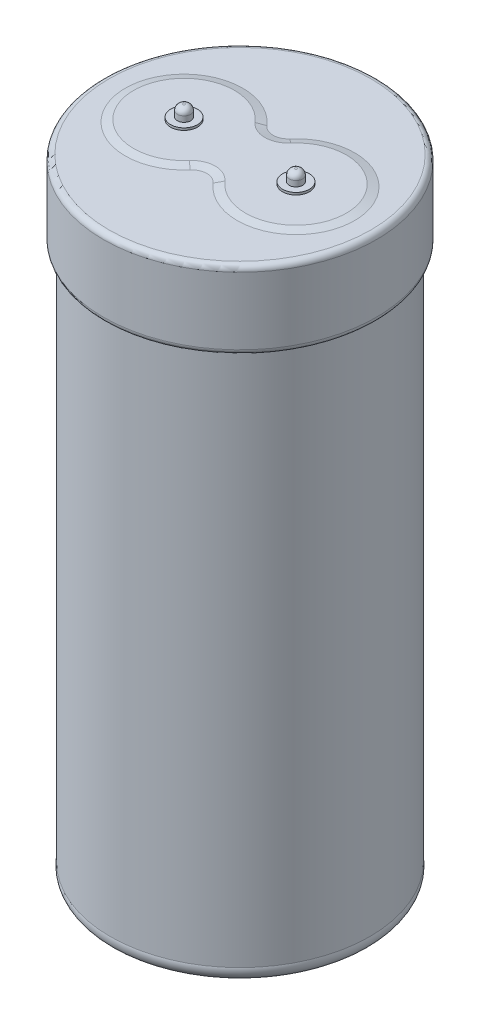
SolidWorks part; units mm, degrees
ref_plane "Front Plane" through (0, 0, 0) normal (0, 0, 1) x (1, 0, 0)
ref_plane "Top Plane" through (0, 0, 0) normal (0, 1, 0) x (1, 0, 0)
ref_plane "Right Plane" through (0, 0, 0) normal (1, 0, 0) x (0, 0, -1)
sketch "Sketch1" plane through (0, 0, 0) normal (0, 0, 1) x (1, 0, 0)
  line L0 (0, 125.4241) -> (0, -154.5759) construction
  line L1 (-1006.3009, 386.8456) -> (941.4092, 386.8456) construction
  line L2 (0, 125.4241) -> (61, 125.4241)
  line L3 (58, 90.4241) -> (58, -148.2441)
  line L4 (53.0864, -154.5759) -> (6, -154.5759)
  line L5 (0, -154.5759) -> (0, 125.4241) construction
  line L6 (6, -154.5759) -> (6, -169.7633)
  line L7 (6, -169.7633) -> (5.1874, -170.5759)
  line L8 (5.1874, -170.5759) -> (0, -170.5759)
  line L9 (0, -170.5759) -> (0, -154.5759) construction
  line L10 (6, -154.5759) -> (0, -154.5759) construction
  line L11 (61, 123.3205) -> (61, 110.2818) construction
  line L12 (0, 125.4241) -> (0, -170.5759)
  line L13 (61, 125.4241) -> (61, 90.4241)
  line L14 (61, 90.4241) -> (58, 90.4241)
  arc A1 (58, -148.2441) -> (53.0864, -154.5759) centre (53.0864, -149.5035) cw
  dimension "D2" = 58
  dimension "D1" = 280
  dimension "D3" = 16
  dimension "D4" = 61
  dimension "D5" = 6
  dimension "D6" = 45
  dimension "D7" = 35
revolve "Revolve1" add sketch "Sketch1" angle 360 about L12
sketch "Sketch2" plane through (0, 125.4241, 0) normal (0, 1, 0) x (1, 0, 0)
  line L0 (-378.6014, 458.2154) -> (210.732, 458.2154) construction
  line L1 (-25, 0) -> (-1.25, 0) construction
  line L2 (0, 45.9854) -> (0, -10.1484) construction
  line L3 (-1.25, 0) -> (0, 0) construction
  line L4 (0, 0) -> (25, 0) construction
  circle A0 centre (25, 0) radius 6
  circle A1 centre (-25, 0) radius 6
  circle A2 centre (25, 0) radius 22.5 construction
  arc A3 (5.1136, 17.1346) -> (-5.1136, 17.1346) centre (0, 21.5407) cw
  arc A4 (5.1136, -17.1346) -> (5.1136, 17.1346) centre (25, 0) ccw
  arc A5 (0, 8.0039) -> (-1.25, 0) centre (25, 0) ccw construction
  arc A6 (-1.25, 0) -> (0, -8.0039) centre (25, 0) ccw construction
  arc A7 (5.1136, 17.1346) -> (0, 8.0039) centre (25, 0) ccw construction
  arc A8 (5.1136, -17.1346) -> (-5.1136, -17.1346) centre (0, -21.5407) ccw
  arc A9 (0, -8.0039) -> (5.1136, -17.1346) centre (25, 0) ccw construction
  arc A10 (-5.1136, -17.1346) -> (-5.1136, 17.1346) centre (-25, 0) cw
  point P6 (0, 0)
  point P16 (0, 0)
  point P17 (0, 0)
  point P23 (0, 0)
  dimension "D1" = 12
  dimension "D2" = 50
  dimension "D3" = 45
  dimension "D4" = 52.5
  dimension "D5" = 6.75
extrude "Boss-Extrude1" add sketch "Sketch2" along normal blind 1
sketch "Sketch3" plane through (0, 125.4241, 0) normal (0, 1, 0) x (1, 0, 0)
  circle A0 centre (-25, 0) radius 6 construction
  circle A1 centre (25, 0) radius 6 construction
  circle A2 centre (-25, 0) radius 6
  circle A3 centre (25, 0) radius 6
extrude "Boss-Extrude2" add sketch "Sketch3" along normal blind 2
sketch "Sketch4" plane through (0, 127.4241, 0) normal (0, 1, 0) x (1, 0, 0)
  line L0 (0, 7.5141) -> (0, -4.8063) construction
  circle A1 centre (25, 0) radius 3
  circle A2 centre (-25, 0) radius 3
  circle A3 centre (-25, 0) radius 3
  dimension "D1" = 3
extrude "Boss-Extrude3" add sketch "Sketch4" along normal blind 5
fillet "Fillet1" radius 2.5 2 edges at (28, 132.4241, 0) (-28, 132.4241, 0)
fillet "Fillet2" radius 2.5 2 edges at (0, 90.4241, 61) (0, 125.4241, 61)
chamfer "Chamfer1" distance 1 angle 75 4 edges at (51.25, 126.4241, 0) (0, 126.4241, -14.7907) (0, 126.4241, 14.7907) (-51.25, 126.4241, 0) first distance on face at (28.1818, 125.9241, 0) first distance on face at (0, 125.9241, -15.9626) first distance on face at (0, 125.9241, 15.9626) first distance on face at (-28.1818, 125.9241, 0)
